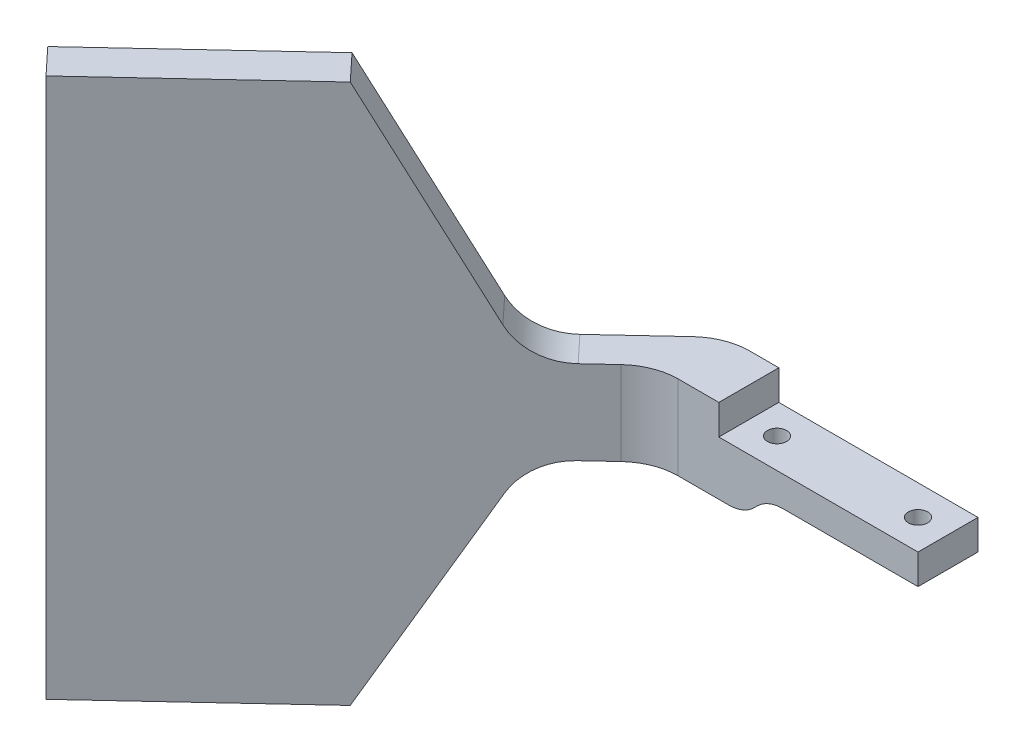
SolidWorks part; units mm, degrees
ref_plane "Front" through (0, 0, 0) normal (0, 0, 1) x (1, 0, 0)
ref_plane "Top" through (0, 0, 0) normal (0, 1, 0) x (1, 0, 0)
ref_plane "Right" through (0, 0, 0) normal (1, 0, 0) x (0, 0, -1)
sketch "Sketch1" plane through (0, 0, 0) normal (0, 1, 0) x (1, 0, 0)
  line L0 (0, 10) -> (0, 0)
  line L1 (0, 0) -> (42, 0)
  line L3 (0, 10) -> (42, 10)
  line L4 (42, 0) -> (42, 10)
  line L9 (0, 10) -> (-58.5083, -44.5599)
  line L10 (-58.5083, -44.5599) -> (-54.4163, -48.948)
  line L11 (0, 10) -> (4.092, 5.6119)
  line L12 (-54.4163, -48.948) -> (4.092, 5.6119)
  line L13 (0, 0) -> (-1.926, 0)
  line L14 (-1.926, 0) -> (0, 1.796)
  line L15 (0, 1.796) -> (0, 0)
  dimension "D1" = 10
  dimension "D2" = 42
  dimension "D3" = 223
  dimension "D4" = 80
  dimension "D5" = 6
  dimension "D6" = 270
extrude "Boss-Extrude1" add sketch "Sketch1" along normal blind 5 contours L10 L12 L1 L0 L9 | L1 L12 L11 L0 | L12 L1 L4 L3 L11 | L13 L0 L12 region at (1.364, 0, -5.8026) region at (-28.2435, 0, 20.3899) region at (21.8174, 0, -4.9666) region at (-0.642, 0, -0.5987)
sketch "Sketch2" plane through (0, 5, 0) normal (0, 1, 0) x (1, 0, 0)
  circle A0 centre (37, 5) radius 1.3
extrude "Cut-Extrude1" cut sketch "Sketch2" against normal blind 10
sketch "Sketch3" plane through (0, 5, 0) normal (0, 1, 0) x (1, 0, 0)
  line L0 (-58.5083, -44.5599) -> (-54.4163, -48.948)
  line L1 (-54.4163, -48.948) -> (-28.1712, -24.474)
  line L2 (-54.4163, -48.948) -> (-1.926, 0) construction
  line L3 (-28.1712, -24.474) -> (-32.2631, -20.0859)
  line L4 (0, 10) -> (-58.5083, -44.5599) construction
  line L5 (-32.2631, -20.0859) -> (-58.5083, -44.5599)
extrude "Boss-Extrude2" add sketch "Sketch3" along normal blind 45
sketch "Sketch4" plane through (0, 0, 0) normal (0, -1, 0) x (1, 0, 0)
  line L0 (-58.5083, 44.5599) -> (-54.4163, 48.948)
  line L1 (-54.4163, 48.948) -> (-28.1712, 24.474)
  line L2 (-54.4163, 48.948) -> (-1.926, 0) construction
  line L3 (-28.1712, 24.474) -> (-32.2631, 20.0859)
  line L4 (0, -10) -> (-58.5083, 44.5599) construction
  line L5 (-32.2631, 20.0859) -> (-58.5083, 44.5599)
extrude "Boss-Extrude3" add sketch "Sketch4" along normal blind 40
sketch "Sketch5" plane through (-4.9878, 0, -5.3488) normal (-0.682, 0, -0.7314) x (-0.7314, 0, 0.682)
  line L0 (37.2943, -40) -> (37.2943, 0)
  line L1 (37.2943, 0) -> (13.889, 0)
  line L2 (-6.82, 0) -> (37.2943, 0) construction
  line L3 (13.889, 0) -> (37.2943, -40)
  line L4 (13.889, 5) -> (37.2943, 50)
  line L5 (-6.82, 5) -> (37.2943, 5) construction
  line L6 (37.2943, 50) -> (37.2943, 5)
  line L7 (37.2943, 5) -> (13.889, 5)
extrude "Boss-Extrude4" add sketch "Sketch5" against normal blind 6
sketch "Sketch6" plane through (0, 0, 0) normal (0, -1, 0) x (1, 0, 0)
  circle A0 centre (37, -5) radius 4.9
  circle A1 centre (37, -5) radius 1.3
extrude "Boss-Extrude5" [suppressed] add sketch "Sketch6" against normal blind 5.9
sketch "Sketch8" plane through (0, 0, 0) normal (0, -1, 0) x (1, 0, 0)
  line L0 (0, -10) -> (-23.7044, 12.1047)
  line L1 (-32.2631, 20.0859) -> (-15.1456, 4.1235) construction
  line L6 (-23.7044, 12.1047) -> (-19.6124, 16.4928)
  line L7 (-28.1712, 24.474) -> (-11.0536, 8.5116) construction
  line L8 (-19.6124, 16.4928) -> (8.7977, -10)
  line L9 (0, -10) -> (42, -10) construction
  line L10 (8.7977, -10) -> (0, -10)
extrude "Boss-Extrude6" add sketch "Sketch8" along normal blind 4
sketch "Sketch9" plane through (0, 5, 0) normal (0, 1, 0) x (1, 0, 0)
  line L3 (-16.8573, -5.7197) -> (-32.2631, -20.0859) construction
  line L4 (-24.5602, -12.9028) -> (0, 10)
  line L6 (-24.5602, -12.9028) -> (-16.7996, -13.8699)
  line L7 (-28.1712, -24.474) -> (-11.0536, -8.5116) construction
  line L9 (-16.7996, -13.8699) -> (8.7977, 10)
  line L10 (0, 10) -> (42, 10) construction
  line L11 (8.7977, 10) -> (0, 10)
  line L12 (42, 0) -> (-1.926, 0) construction
  line L13 (8.7977, 0) -> (-1.926, 0)
  line L14 (-1.926, 0) -> (8.7977, 10)
  line L15 (8.7977, 10) -> (17.9505, 10)
  line L16 (17.9505, 10) -> (17.9505, 0)
  line L17 (17.9505, 0) -> (8.7977, 0)
  line M3 (-1.926, 0) -> (42, 0)
  line M6 (42, 10) -> (0, 10)
sketch "Sketch10" plane through (0, 5, 0) normal (0, 1, 0) x (1, 0, 0)
  line L0 (8.7977, 10) -> (8.7977, 0)
  line L1 (8.7977, 0) -> (-1.926, 0)
  line L2 (-1.926, 0) -> (-16.7996, -13.8699)
  line L3 (-16.7996, -13.8699) -> (-20.8916, -9.4817)
  line L4 (-20.8916, -9.4817) -> (0, 10)
  line L5 (0, 10) -> (8.7977, 10)
extrude "Boss-Extrude7" add sketch "Sketch10" along normal blind 5
extrude "Boss-Extrude8" add sketch "Sketch9" against normal blind 9 contours L16 L9 M6 M3 region at (10.3631, 5, -4.3843)
chamfer "Chamfer1" distance 5 angle 45 1 edges at (17.9505, -4, -5)
fillet "Fillet2" radius 6 2 edges at (16.9505, 0, -5) (12.9505, -4, -5)
sketch "Sketch11" plane through (0, 5, 0) normal (0, 1, 0) x (1, 0, 0)
  circle A0 centre (13.5, 5) radius 1.6
extrude "Cut-Extrude2" cut sketch "Sketch11" against normal blind 10
fillet "Fillet3" radius 10 4 edges at (0, 3, -10) (-14.8113, -4, 7.9138) (-15.0015, 10, 8.0911) (-1.926, 3, 0)
sketch "Sketch12" plane through (0, 5, 0) normal (0, 1, 0) x (1, 0, 0)
  circle A0 centre (37, 5) radius 1.6
extrude "Cut-Extrude3" cut sketch "Sketch12" against normal through all both and the other way through all
